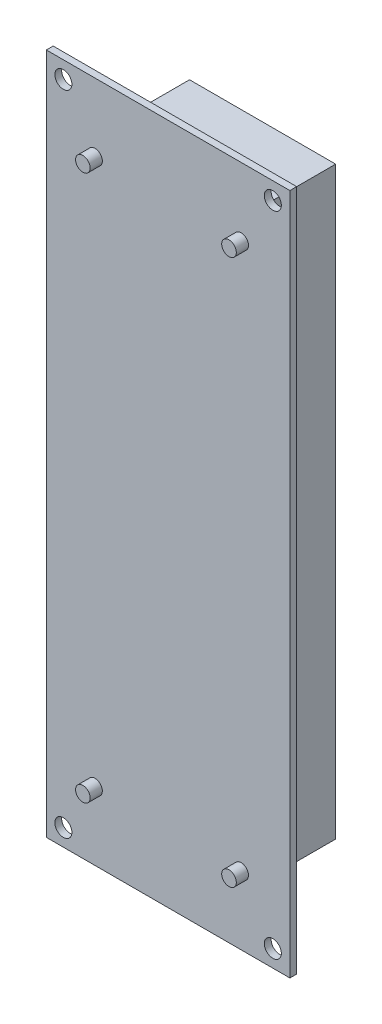
SolidWorks part; units mm, degrees
ref_plane "Front Plane" through (0, 0, 0) normal (0, 0, 1) x (1, 0, 0)
ref_plane "Top Plane" through (0, 0, 0) normal (0, 1, 0) x (1, 0, 0)
ref_plane "Right Plane" through (0, 0, 0) normal (1, 0, 0) x (0, 0, -1)
sketch "Sketch1" plane through (0, 0, 0) normal (0, 0, 1) x (1, 0, 0)
  line L1 (-25, -70) -> (25, -70)
  line L2 (-25, -70) -> (-25, 70)
  line L3 (-25, 70) -> (25, 70)
  line L4 (25, -70) -> (25, 70)
  line L5 (-25, -70) -> (25, 70) construction
  line L6 (-25, 70) -> (25, -70) construction
  point P0 (0, 0)
  dimension "D1" = 140
  dimension "D2" = 50
extrude "Boss-Extrude1" add sketch "Sketch1" along normal mid plane 1.4
sketch "Sketch3" plane through (0, 0, -0.7) normal (0, 0, -1) x (-1, 0, 0)
  line L12 (-15, 60) -> (-15, -60)
  line L13 (-15, -60) -> (15, -60)
  line L14 (15, -60) -> (15, 60)
  line L15 (15, 60) -> (-15, 60)
  line L16 (-15, 60) -> (-15, -60)
  line L17 (-15, -60) -> (15, -60)
  line L18 (15, -60) -> (15, 60)
  line L19 (15, 60) -> (-15, 60)
  dimension "D1" = 10
extrude "Boss-Extrude2" add sketch "Sketch3" along normal blind 18
sketch "Sketch4" plane through (0, 0, -0.7) normal (0, 0, -1) x (-1, 0, 0)
  line L0 (25, 70) -> (25, -70) construction
  line L1 (-21.5, -66.5) -> (21.5, -66.5) construction
  line L2 (-21.5, -66.5) -> (-21.5, 66.5) construction
  line L3 (-21.5, 66.5) -> (21.5, 66.5) construction
  line L4 (21.5, -66.5) -> (21.5, 66.5) construction
  line L5 (-21.5, -66.5) -> (21.5, 66.5) construction
  line L6 (-21.5, 66.5) -> (21.5, -66.5) construction
  line L7 (-25, 70) -> (25, 70) construction
  circle A0 centre (-21.5, 66.5) radius 1.75
  circle A1 centre (21.5, 66.5) radius 1.75
  circle A2 centre (-21.5, -66.5) radius 1.75
  circle A3 centre (21.5, -66.5) radius 1.75
  point P0 (0, 0)
  dimension "D3" = 3.5
  dimension "D1" = 3.5
  dimension "D2" = 3.5
extrude "Cut-Extrude1" cut sketch "Sketch4" against normal up to surface (1.4 mm away) up to face at (0, 0, 0.7)
sketch "Sketch5" plane through (0, 0, 0.7) normal (0, 0, 1) x (1, 0, 0)
  line L0 (25, 70) -> (-25, 70) construction
  line L1 (-15, -56) -> (15, -56) construction
  line L2 (-15, -56) -> (-15, 56) construction
  line L3 (-15, 56) -> (15, 56) construction
  line L4 (15, -56) -> (15, 56) construction
  line L5 (-15, -56) -> (15, 56) construction
  line L6 (-15, 56) -> (15, -56) construction
  line L7 (25, -70) -> (25, 70) construction
  circle A0 centre (15, 56) radius 1.5
  circle A1 centre (-15, 56) radius 1.5
  circle A2 centre (-15, -56) radius 1.5
  circle A3 centre (15, -56) radius 1.5
  point P0 (0, 0)
  dimension "D3" = 3
  dimension "D1" = 14
  dimension "D2" = 10
extrude "Boss-Extrude3" add sketch "Sketch5" along normal blind 2.5
